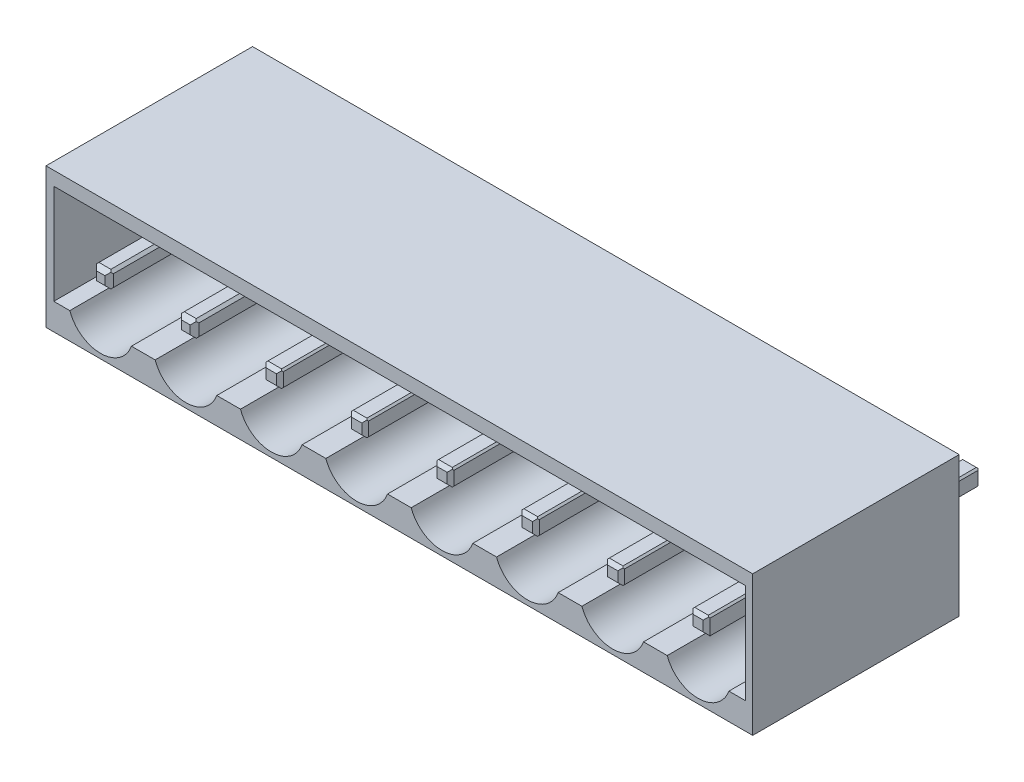
SolidWorks part; units mm, degrees
ref_plane "Спереди" through (0, 0, 0) normal (0, 0, 1) x (1, 0, 0)
ref_plane "Сверху" through (0, 0, 0) normal (0, 1, 0) x (1, 0, 0)
ref_plane "Справа" through (0, 0, 0) normal (1, 0, 0) x (0, 0, -1)
sketch "Эскиз1" plane through (0, 0, 0) normal (0, 0, 1) x (1, 0, 0)
  line L1 (-20.7, 4.1) -> (20.7, 4.1)
  line L2 (-20.7, 4.1) -> (-20.7, -4.1)
  line L3 (-20.7, -4.1) -> (20.7, -4.1)
  line L4 (20.7, 4.1) -> (20.7, -4.1)
  line L5 (-20.7, 4.1) -> (20.7, -4.1) construction
  line L6 (-20.7, -4.1) -> (20.7, 4.1) construction
  point P0 (0, 0)
  dimension "D1" = 8.2
  dimension "D2" = 41.4
extrude "Бобышка-Вытянуть1" add sketch "Эскиз1" along normal blind 12.1
sketch "Эскиз4" plane through (0, 0, 12.1) normal (0, 0, 1) x (1, 0, 0)
  circle A0 centre (-17.5, 0) radius 1.25
  circle A1 centre (-12.5, 0) radius 1.25
  circle A2 centre (-7.5, 0) radius 1.25
  circle A3 centre (-2.5, 0) radius 1.25
  circle A4 centre (2.5, 0) radius 1.25
  circle A5 centre (7.5, 0) radius 1.25
  circle A6 centre (12.5, 0) radius 1.25
  circle A7 centre (17.5, 0) radius 1.25
  dimension "D1" = 2.5
  dimension "D2" = 3.2
  dimension "D5" = 2
  dimension "D3" = 2
  dimension "D4" = 2
  dimension "D6" = 3
  dimension "D7" = 2
extrude "Вырез-Вытянуть3" cut sketch "Эскиз4" against normal blind 8
sketch "Эскиз5" plane through (0, 0, 12.1) normal (0, 0, 1) x (1, 0, 0)
  line L0 (-20.2456, 0) -> (-20.2456, 3.2929)
  line L1 (-20.2456, 3.2929) -> (-9.7215, 3.2929)
  line L4 (-20.2456, -2.549) -> (-20.2456, 0)
  line L5 (-10.6942, -2.549) -> (-9.3058, -2.549)
  line L6 (-19.3058, -2.549) -> (-20.2456, -2.549)
  line L7 (-15.6942, -2.549) -> (-14.3058, -2.549)
  line L11 (-9.7215, 3.2929) -> (-4.7215, 3.2929)
  line L13 (-10.6942, -2.549) -> (-9.3058, -2.549) [skipped]
  line L15 (-5.6942, -2.549) -> (-4.3058, -2.549)
  line L16 (-4.7215, 3.2929) -> (0.2785, 3.2929)
  line L17 (4.3058, -2.549) -> (5.6942, -2.549)
  line L20 (-0.6942, -2.549) -> (0.6942, -2.549)
  line L21 (0.2785, 3.2929) -> (10.2785, 3.2929)
  line L22 (14.3058, -2.549) -> (15.6942, -2.549)
  line L23 (19.3058, -2.549) -> (20.2785, -2.549)
  line L24 (20.2785, 3.2929) -> (20.2785, -2.549)
  line L25 (10.2785, 3.2929) -> (20.2785, 3.2929)
  line L26 (9.3058, -2.549) -> (10.6942, -2.549)
  arc A1 (-9.3058, -2.549) -> (-5.6942, -2.549) centre (-7.5, -1.9) ccw
  arc A2 (-4.3058, -2.549) -> (-0.6942, -2.549) centre (-2.5, -1.9) ccw
  arc A4 (0.6942, -2.549) -> (4.3058, -2.549) centre (2.5, -1.9) ccw
  arc A5 (-19.3058, -2.549) -> (-15.6942, -2.549) centre (-17.5, -1.9) ccw
  arc A6 (-14.3058, -2.549) -> (-10.6942, -2.549) centre (-12.5, -1.9) ccw
  arc A7 (5.6942, -2.549) -> (9.3058, -2.549) centre (7.5, -1.9) ccw
  arc A8 (10.6942, -2.549) -> (14.3058, -2.549) centre (12.5, -1.9) ccw
  arc A9 (15.6942, -2.549) -> (19.3058, -2.549) centre (17.5, -1.9) ccw
  dimension "D1" = 3.2
  dimension "D2" = 2.2
  dimension "D3" = 2
  dimension "D4" = 2
  dimension "D5" = 2
  dimension "D6" = 2
  dimension "D7" = 2
extrude "Вырез-Вытянуть4" cut sketch "Эскиз5" against normal blind 7.8
sketch "Эскиз7" plane through (0, 0, 4.1) normal (0, 0, 1) x (1, 0, 0)
  line L0 (-13, 0.5) -> (-12, 0.5)
  line L1 (-18, 0.5) -> (-17, 0.5)
  line L2 (-18, 0.5) -> (-18, -0.5)
  line L3 (-18, -0.5) -> (-17, -0.5)
  line L4 (-17, 0.5) -> (-17, -0.5)
  line L5 (-18, 0.5) -> (-17, -0.5) construction
  line L6 (-18, -0.5) -> (-17, 0.5) construction
  line L7 (-13, 0.5) -> (-13, -0.5)
  line L8 (-13, -0.5) -> (-12, -0.5)
  line L9 (-12, 0.5) -> (-12, -0.5)
  line L10 (-13, 0.5) -> (-12, -0.5) construction
  line L11 (-13, -0.5) -> (-12, 0.5) construction
  line L12 (-8, 0.5) -> (-7, 0.5)
  line L13 (-8, 0.5) -> (-8, -0.5)
  line L14 (-8, -0.5) -> (-7, -0.5)
  line L15 (-7, 0.5) -> (-7, -0.5)
  line L16 (-8, 0.5) -> (-7, -0.5) construction
  line L17 (-8, -0.5) -> (-7, 0.5) construction
  line L18 (-3, 0.5) -> (-2, 0.5)
  line L19 (-3, 0.5) -> (-3, -0.5)
  line L20 (-3, -0.5) -> (-2, -0.5)
  line L21 (-2, 0.5) -> (-2, -0.5)
  line L22 (-3, 0.5) -> (-2, -0.5) construction
  line L23 (-3, -0.5) -> (-2, 0.5) construction
  line L24 (2, 0.5) -> (3, 0.5)
  line L25 (2, 0.5) -> (2, -0.5)
  line L26 (2, -0.5) -> (3, -0.5)
  line L27 (3, 0.5) -> (3, -0.5)
  line L28 (7, 0.5) -> (8, 0.5)
  line L29 (7, 0.5) -> (7, -0.5)
  line L30 (7, -0.5) -> (8, -0.5)
  line L31 (8, 0.5) -> (8, -0.5)
  line L32 (2, 0.5) -> (3, -0.5) construction
  line L33 (2, -0.5) -> (3, 0.5) construction
  line L34 (7, 0.5) -> (8, -0.5) construction
  line L35 (7, -0.5) -> (8, 0.5) construction
  line L36 (12, 0.5) -> (13, 0.5)
  line L37 (12, 0.5) -> (12, -0.5)
  line L38 (12, -0.5) -> (13, -0.5)
  line L39 (13, 0.5) -> (13, -0.5)
  line L40 (17, 0.5) -> (18, 0.5)
  line L41 (17, 0.5) -> (17, -0.5)
  line L42 (17, -0.5) -> (18, -0.5)
  line L43 (18, 0.5) -> (18, -0.5)
  line L44 (12, 0.5) -> (13, -0.5) construction
  line L45 (12, -0.5) -> (13, 0.5) construction
  line L46 (17, 0.5) -> (18, -0.5) construction
  line L47 (17, -0.5) -> (18, 0.5) construction
  point P0 (-17.5, 0)
  point P7 (-12.5, 0)
  point P12 (-7.5, 0)
  point P17 (-2.5, 0)
  point P23 (2.5, 0)
  point P28 (7.5, 0)
  point P33 (12.5, 0)
  point P38 (17.5, 0)
  dimension "D1" = 1
  dimension "D2" = 1
  dimension "D3" = 2
  dimension "D4" = 2
  dimension "D5" = 2
  dimension "D6" = 2
  dimension "D7" = 2
extrude "Бобышка-Вытянуть2" add sketch "Эскиз7" along normal blind 8
chamfer "Фаска1" distance 0.15 angle 45 8 edges at (-13, -0.5, 8.1) (-13, 0.5, 8.1) (-12, 0.5, 8.1) (-12, -0.5, 8.1) (-17, -0.5, 8.1) (-17, 0.5, 8.1) (-18, -0.5, 8.1) (-18, 0.5, 8.1)
chamfer "Фаска2" distance 0.25 angle 45 8 edges at (-13, 0, 12.1) (-12.5, 0.5, 12.1) (-12, 0, 12.1) (-12.5, -0.5, 12.1) (-17, 0, 12.1) (-17.5, -0.5, 12.1) (-18, 0, 12.1) (-17.5, 0.5, 12.1)
sketch "Эскиз8" plane through (0, -4.1, 0) normal (0, 0, 1) x (-1, 0, 0)
  line L0 (13, -4.25) -> (12, -4.25)
  line L1 (18, -4.25) -> (17, -4.25)
  line L2 (18, -4.25) -> (18, -3.25)
  line L3 (18, -3.25) -> (17, -3.25)
  line L4 (17, -4.25) -> (17, -3.25)
  line L5 (18, -4.25) -> (17, -3.25) construction
  line L6 (18, -3.25) -> (17, -4.25) construction
  line L7 (13, -4.25) -> (13, -3.25)
  line L8 (13, -3.25) -> (12, -3.25)
  line L9 (12, -4.25) -> (12, -3.25)
  line L10 (13, -4.25) -> (12, -3.25) construction
  line L11 (13, -3.25) -> (12, -4.25) construction
  line L12 (8, -4.25) -> (7, -4.25)
  line L13 (8, -4.25) -> (8, -3.25)
  line L14 (8, -3.25) -> (7, -3.25)
  line L15 (7, -4.25) -> (7, -3.25)
  line L16 (8, -4.25) -> (7, -3.25) construction
  line L17 (8, -3.25) -> (7, -4.25) construction
  line L18 (3, -4.25) -> (2, -4.25)
  line L19 (3, -4.25) -> (3, -3.25)
  line L20 (3, -3.25) -> (2, -3.25)
  line L21 (2, -4.25) -> (2, -3.25)
  line L22 (3, -4.25) -> (2, -3.25) construction
  line L23 (3, -3.25) -> (2, -4.25) construction
  line L24 (-2, -4.25) -> (-3, -4.25)
  line L25 (-2, -4.25) -> (-2, -3.25)
  line L26 (-2, -3.25) -> (-3, -3.25)
  line L27 (-3, -4.25) -> (-3, -3.25)
  line L28 (-7, -4.25) -> (-8, -4.25)
  line L29 (-7, -4.25) -> (-7, -3.25)
  line L30 (-7, -3.25) -> (-8, -3.25)
  line L31 (-8, -4.25) -> (-8, -3.25)
  line L32 (-2, -4.25) -> (-3, -3.25) construction
  line L33 (-2, -3.25) -> (-3, -4.25) construction
  line L34 (-7, -4.25) -> (-8, -3.25) construction
  line L35 (-7, -3.25) -> (-8, -4.25) construction
  line L36 (-12, -4.25) -> (-13, -4.25)
  line L37 (-12, -4.25) -> (-12, -3.25)
  line L38 (-12, -3.25) -> (-13, -3.25)
  line L39 (-13, -4.25) -> (-13, -3.25)
  line L40 (-17, -4.25) -> (-18, -4.25)
  line L41 (-17, -4.25) -> (-17, -3.25)
  line L42 (-17, -3.25) -> (-18, -3.25)
  line L43 (-18, -4.25) -> (-18, -3.25)
  line L44 (-12, -4.25) -> (-13, -3.25) construction
  line L45 (-12, -3.25) -> (-13, -4.25) construction
  line L46 (-17, -4.25) -> (-18, -3.25) construction
  line L47 (-17, -3.25) -> (-18, -4.25) construction
  point P0 (17.5, -3.75)
  point P7 (12.5, -3.75)
  point P12 (7.5, -3.75)
  point P18 (2.5, -3.75)
  point P23 (-2.5, -3.75)
  point P28 (-7.5, -3.75)
  point P33 (-12.5, -3.75)
  point P38 (-17.5, -3.75)
  dimension "D1" = 1
  dimension "D2" = 1
  dimension "D3" = 3.2
  dimension "D4" = 4.45
  dimension "D5" = 2
  dimension "D6" = 2
  dimension "D7" = 2
  dimension "D8" = 2
  dimension "D9" = 2
extrude "Бобышка-Вытянуть3" add sketch "Эскиз8" against normal blind 4
chamfer "Фаска6" distance 0.1 angle 45 4 edges at (-8, -0.5, 8.1) (-7, -0.5, 8.1) (-7, 0.5, 8.1) (-8, 0.5, 8.1)
chamfer "Фаска7" distance 0.2 angle 45 4 edges at (-7, 0, 12.1) (-7.5, -0.5, 12.1) (-8, 0, 12.1) (-7.5, 0.5, 12.1)
chamfer "Фаска10" distance 0.1 angle 45 12 edges at (-18, -0.85, -2) (-18, 0.15, -2) (-13, -0.85, -2) (-13, 0.15, -2) (-8, -0.85, -2) (-8, 0.15, -2) (-17, -0.85, -2) (-12, -0.85, -2) (-7, -0.85, -2) (-17, 0.15, -2) (-12, 0.15, -2) (-7, 0.15, -2)
chamfer "Фаска11" distance 0.2 angle 45 12 edges at (-17, -0.35, -4) (-17.5, 0.15, -4) (-18, -0.35, -4) (-17.5, -0.85, -4) (-12.5, -0.85, -4) (-13, -0.35, -4) (-12.5, 0.15, -4) (-12, -0.35, -4) (-8, -0.35, -4) (-7.5, 0.15, -4) (-7, -0.35, -4) (-7.5, -0.85, -4)
chamfer "Фаска12" distance 0.1 angle 45 20 edges at (-3, 0.15, -2) (-3, -0.85, -2) (-2, 0.15, -2) (-2, -0.85, -2) (7, -0.5, 8.1) (2, -0.5, 8.1) (2, 0.5, 8.1) (3, 0.5, 8.1) (3, -0.5, 8.1) (8, -0.5, 8.1) (7, 0.5, 8.1) (8, 0.5, 8.1) (7, -0.85, -2) (7, 0.15, -2) (8, -0.85, -2) (8, 0.15, -2) (3, -0.85, -2) (3, 0.15, -2) (2, -0.85, -2) (2, 0.15, -2)
chamfer "Фаска13" distance 0.2 angle 45 4 edges at (-2.5, 0.15, -4) (-2, -0.35, -4) (-3, -0.35, -4) (-2.5, -0.85, -4)
chamfer "Фаска14" distance 0.1 angle 45 18 edges at (-2, 0.5, 8.1) (-2, -0.5, 8.1) (-3, -0.5, 8.1) (-3, 0.5, 8.1) (12, -0.5, 8.1) (13, -0.5, 8.1) (18, 0.5, 8.1) (17, 0.5, 8.1) (12, 0.5, 8.1) (13, 0.5, 8.1) (13, -0.85, -2) (18, -0.85, -2) (18, 0.15, -2) (17, 0.15, -2) (17, -0.85, -2) (12, -0.85, -2) (13, 0.15, -2) (12, 0.15, -2)
chamfer "Фаска15" distance 0.2 angle 45 36 edges at (-3, 0, 12.1) (-2.5, -0.5, 12.1) (-2, 0, 12.1) (-2.5, 0.5, 12.1) (2, -0.35, -4) (2.5, -0.85, -4) (3, -0.35, -4) (2.5, 0.15, -4) (7, -0.35, -4) (7.5, -0.85, -4) (8, -0.35, -4) (7.5, 0.15, -4) (8, 0, 12.1) (7.5, -0.5, 12.1) (7, 0, 12.1) (7.5, 0.5, 12.1) (2.5, -0.5, 12.1) (3, 0, 12.1) (2, 0, 12.1) (2.5, 0.5, 12.1) (17.5, -0.85, -4) (18, -0.35, -4) (17, -0.35, -4) (17.5, 0.15, -4) (13, -0.35, -4) (12.5, -0.85, -4) (12, -0.35, -4) (12.5, 0.15, -4) (18, -0.05, 12.1) (17.5, -0.5, 12.1) (17, -0.05, 12.1) (17.5, 0.5, 12.1) (12, 0, 12.1) (12.5, -0.5, 12.1) (13, 0, 12.1) (12.5, 0.5, 12.1)
